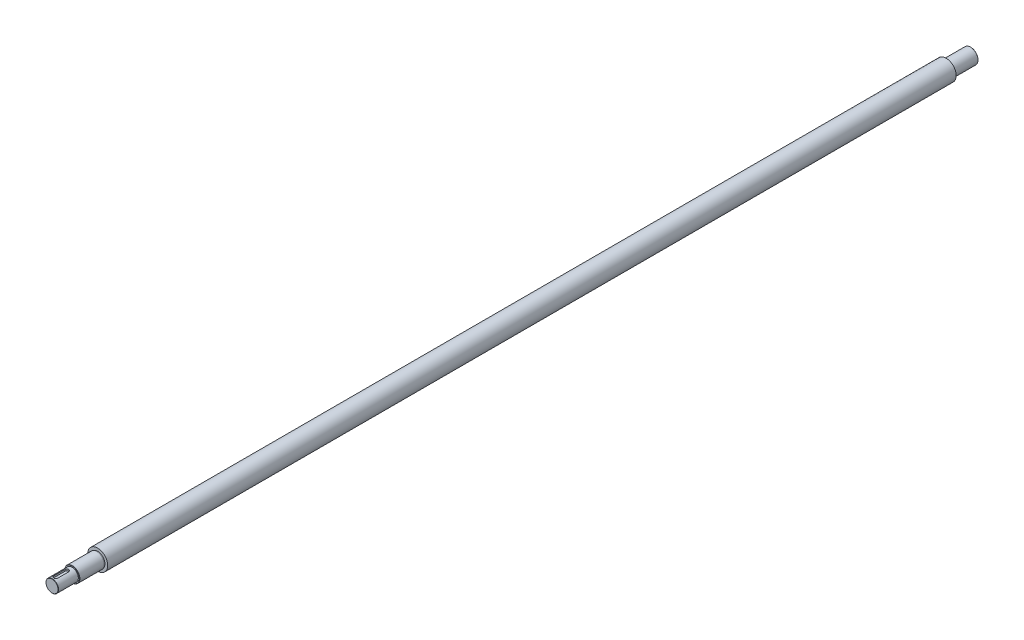
SolidWorks part; units mm, degrees
ref_plane "前视基准面" through (0, 0, 0) normal (0, 0, 1) x (1, 0, 0)
ref_plane "上视基准面" through (0, 0, 0) normal (0, 1, 0) x (1, 0, 0)
ref_plane "右视基准面" through (0, 0, 0) normal (1, 0, 0) x (0, 0, -1)
other "Configuration Table"
sketch "草图1" plane through (0, 0, 0) normal (0, 0, 1) x (1, 0, 0)
  circle A0 centre (0, 0) radius 12.5
  dimension "D1" = 25
extrude "凸台-拉伸1" add sketch "草图1" along normal blind 40
chamfer "倒角1" distance 0.5 angle 45 1 edges at (12.5, 0, 40)
sketch "草图2" plane through (0, 0, 0) normal (0, 0, -1) x (-1, 0, 0)
  circle A0 centre (0, 0) radius 15
  dimension "D1" = 30
extrude "凸台-拉伸2" add sketch "草图2" along normal blind 49
chamfer "倒角2" distance 0.5 angle 45 1 edges at (-15, 0, 0)
ref_plane "基准面1" through (0, 12.5, 0) normal (0, 1, 0) x (1, 0, 0)
sketch "草图5" plane through (0, 12.5, 0) normal (0, 1, 0) x (1, 0, 0)
  line L0 (0, -33) -> (0, -11) construction
  line L1 (0, -39.5) -> (0, 0) construction
  line L2 (-4, -33) -> (-4, -11)
  line L3 (4, -33) -> (4, -11)
  line L5 (-12, -40) -> (12, -40) construction
  arc A0 (-4, -33) -> (4, -33) centre (0, -33) ccw
  arc A1 (4, -11) -> (-4, -11) centre (0, -11) ccw
  point P5 (0, -22)
  point P10 (0, -7)
  point P11 (0, -37)
  dimension "D1" = 30
  dimension "D2" = 3
  dimension "D3" = 8
extrude "切除-拉伸1" cut sketch "草图5" against normal blind 4
sketch "草图6" plane through (0, 0, 0) normal (0, 0, 1) x (1, 0, 0)
  circle A0 centre (0, 0) radius 15
curve "螺旋线/涡状线1" [suppressed] pitch 1.5 height 20 turns 13.3333
sketch "草图10" plane through (0, 0, 0) normal (0, 1, 0) x (1, 0, 0)
  line L0 (13, 0.5) -> (15, 1.6547)
  line L1 (15, 1.6547) -> (15, -0.6547)
  line L2 (15, -0.6547) -> (13, 0.5)
  point P4 (15, 0.5)
  dimension "D1" = 60
  dimension "D2" = 2
sweep "切除-扫描1" [suppressed] cut profiles "草图10" path "螺旋线/涡状线1"
sketch "草图11" plane through (0, 0, -49) normal (0, 0, -1) x (-1, 0, 0)
  circle A0 centre (0, 0) radius 14.5
  dimension "D1" = 29
extrude "凸台-拉伸3" add sketch "草图11" along normal blind 2
sketch "草图12" plane through (0, 0, -51) normal (0, 0, -1) x (-1, 0, 0)
  circle A0 centre (0, 0) radius 20
  dimension "D1" = 40
extrude "凸台-拉伸4" add sketch "草图12" along normal blind 1691
sketch "草图13" plane through (0, 0, -1742) normal (0, 0, -1) x (-1, 0, 0)
  circle A0 centre (0, 0) radius 14.5
  dimension "D1" = 29
extrude "凸台-拉伸5" add sketch "草图13" along normal blind 2
sketch "草图14" plane through (0, 0, -1744) normal (0, 0, -1) x (-1, 0, 0)
  circle A0 centre (0, 0) radius 15
  dimension "D1" = 30
extrude "凸台-拉伸6" add sketch "草图14" along normal blind 47
chamfer "倒角3" distance 0.5 angle 45 1 edges at (-15, 0, -1791)
sketch "草图15" plane through (0, 0, -1791) normal (0, 0, -1) x (-1, 0, 0)
  circle A0 centre (0, 0) radius 15
sketch "草图16" plane through (0, 0, 0) normal (0, 1, 0) x (1, 0, 0)
  line L0 (13, 1790.5) -> (15, 1791.6547)
  line L1 (15, 1791.6547) -> (15, 1789.3453)
  line L2 (15, 1789.3453) -> (13, 1790.5)
  point P4 (15, 1790.5)
  dimension "D1" = 60
  dimension "D2" = 2
curve "螺旋线/涡状线2" [suppressed] pitch 1.5 height 20 turns 13.3333
sweep "切除-扫描2" [suppressed] cut profiles "草图16" path "螺旋线/涡状线2"
